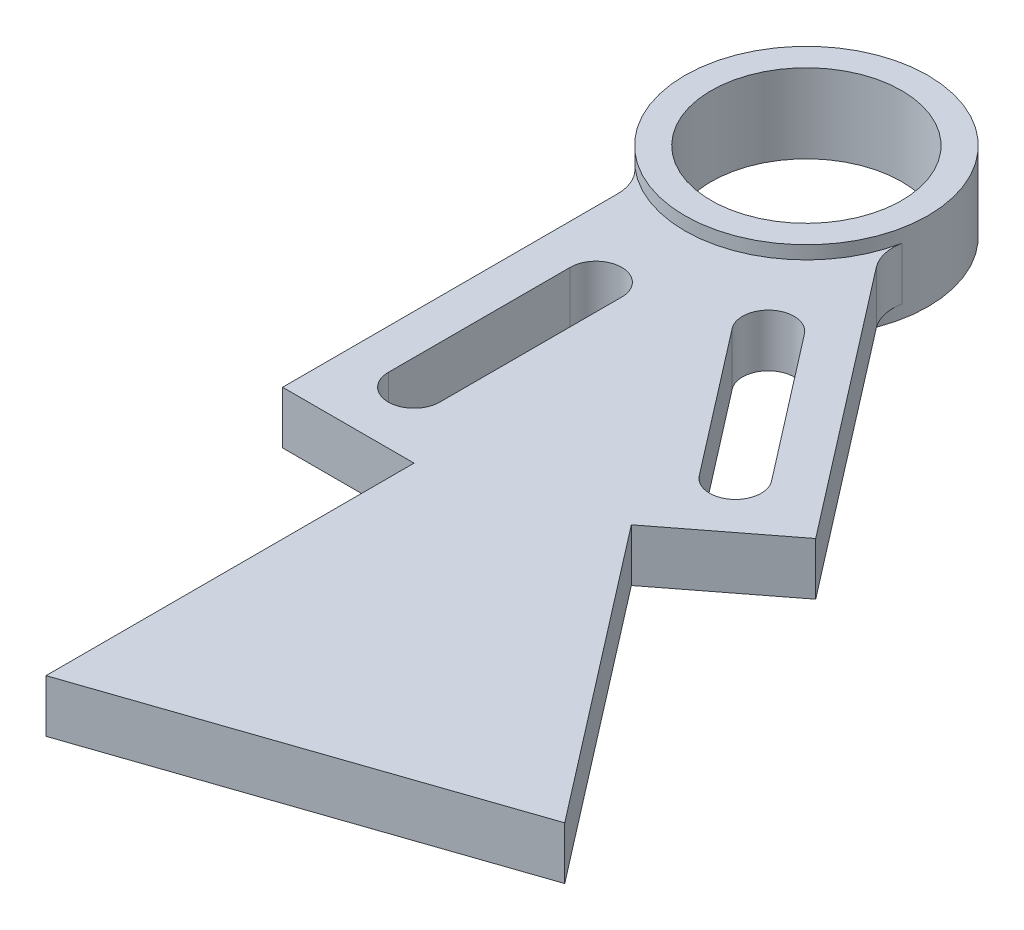
SolidWorks part; units mm, degrees
material "AISI 4130 Steel, normalized at 870C"
ref_plane "Front Plane" through (0, 0, 0) normal (0, 0, 1) x (1, 0, 0)
ref_plane "Top Plane" through (0, 0, 0) normal (0, 1, 0) x (1, 0, 0)
ref_plane "Right Plane" through (0, 0, 0) normal (1, 0, 0) x (0, 0, -1)
sketch "Sketch1" plane through (0, 0, 0) normal (0, 1, 0) x (1, 0, 0)
  line L0 (0, -50.4952) -> (0, -14.6812) construction
  line L1 (30.8439, -39.9802) -> (8.9677, -11.624) construction
  line L2 (0, -47.3837) -> (0, -25.4127) construction
  line L5 (-3.1115, -47.3837) -> (-3.1115, -25.4127)
  line L8 (-7.9375, -55.3212) -> (7.9375, -55.3212)
  line L9 (27.5071, -48.6497) -> (40.0764, -38.9528)
  line L10 (-7.9375, -55.3212) -> (-7.9375, -12.3505)
  line L11 (40.0764, -38.9528) -> (13.8286, -4.9302)
  line L12 (7.9375, -55.3212) -> (7.9375, -99.7712)
  line L13 (27.5071, -48.6497) -> (54.6585, -83.8436)
  line L14 (7.9375, -99.7712) -> (54.6585, -83.8436)
  line L15 (0, -14.6812) -> (0, 0) construction
  line L16 (0, -55.3212) -> (0, -50.4952) construction
  line L17 (33.7918, -43.8013) -> (30.8439, -39.9802)
  line L18 (3.1115, -47.3837) -> (3.1115, -25.4127)
  line L19 (15.5228, -20.1208) -> (28.9433, -37.5167) construction
  line L20 (17.9864, -18.2202) -> (31.4069, -35.6161)
  line L21 (13.0592, -22.0214) -> (26.4797, -39.4173)
  line L22 (8.9677, -11.624) -> (0, 0) construction
  line L23 (0, 0) -> (21.3094, -62.5075) construction
  line L25 (198.9178, -257.8397) -> (14.2221, -18.4349) construction
  line L27 (0, 0) -> (31.298, -91.8074) construction
  circle A0 centre (0, 0) radius 11.5062
  circle A1 centre (0, 0) radius 14.6812
  arc A2 (-3.1115, -47.3837) -> (3.1115, -47.3837) centre (0, -47.3837) ccw
  arc A3 (3.1115, -25.4127) -> (-3.1115, -25.4127) centre (0, -25.4127) ccw
  arc A4 (17.9864, -18.2202) -> (13.0592, -22.0214) centre (15.5228, -20.1208) ccw
  arc A5 (26.4797, -39.4173) -> (31.4069, -35.6161) centre (28.9433, -37.5167) ccw
  point P9 (0, -36.3982)
  point P14 (22.2331, -28.8188)
  point P23 (0, -55.3212)
  point P26 (33.7918, -43.8013)
  point P33 (0, -50.4952)
  point P36 (30.8439, -39.9802)
  point P38 (0, -22.3012)
  dimension "D2" = 29.3624
  dimension "D3" = 40.64
  dimension "D4" = 4.826
  dimension "D6" = 44.45
  dimension "D7" = 7.9375
  dimension "D5" = 4.826
  dimension "D8" = 7.62
  dimension "D9" = 66.04
extrude "Bearing extrude" add sketch "Sketch1" along normal mid plane 9.525 contours A1 A0 region at (-6.8368, 0, -12.521)
extrude "Boss-Extrude2" add sketch "Sketch1<5>" along normal mid plane 6.35 contours A1 L10 L8 L12 L14 L13 L9 L11 A4 A2 region at (19.0286, 0, 55.8173)
sketch "Sketch1<5>" plane through (0, 0, 0) normal (0, 1, 0) x (1, 0, 0) same geometry as "Sketch1"
sketch3d "Tab Point"
  line L0 (21.3094, 0, 62.5075) -> (21.3094, 22.225, 62.5075) construction
  line L1 (0, 0, 0) -> (21.3094, 0, 62.5075) construction
  line L2 (0, 0, 0) -> (31.298, 0, 91.8074) construction
  dimension "D1" = 22.225
fillet "Fillet1" radius 5.08 2 edges at (13.8286, 0, 4.9302) (-7.9375, 0, 12.3505)
equation "\"Apex_thickness\"= .25"
equation "\"Bearing_diameter\"= .906"
equation "\"A-arm_angle\"= 32.91"
equation "\"D1@Sketch1\"=\"Bearing_diameter\""
equation "\"D1@Boss-Extrude2\"= \"Apex_thickness\""
equation "\"apex slot\"= 1.4"
equation "\"tube diameter\"= 5 / 8"
